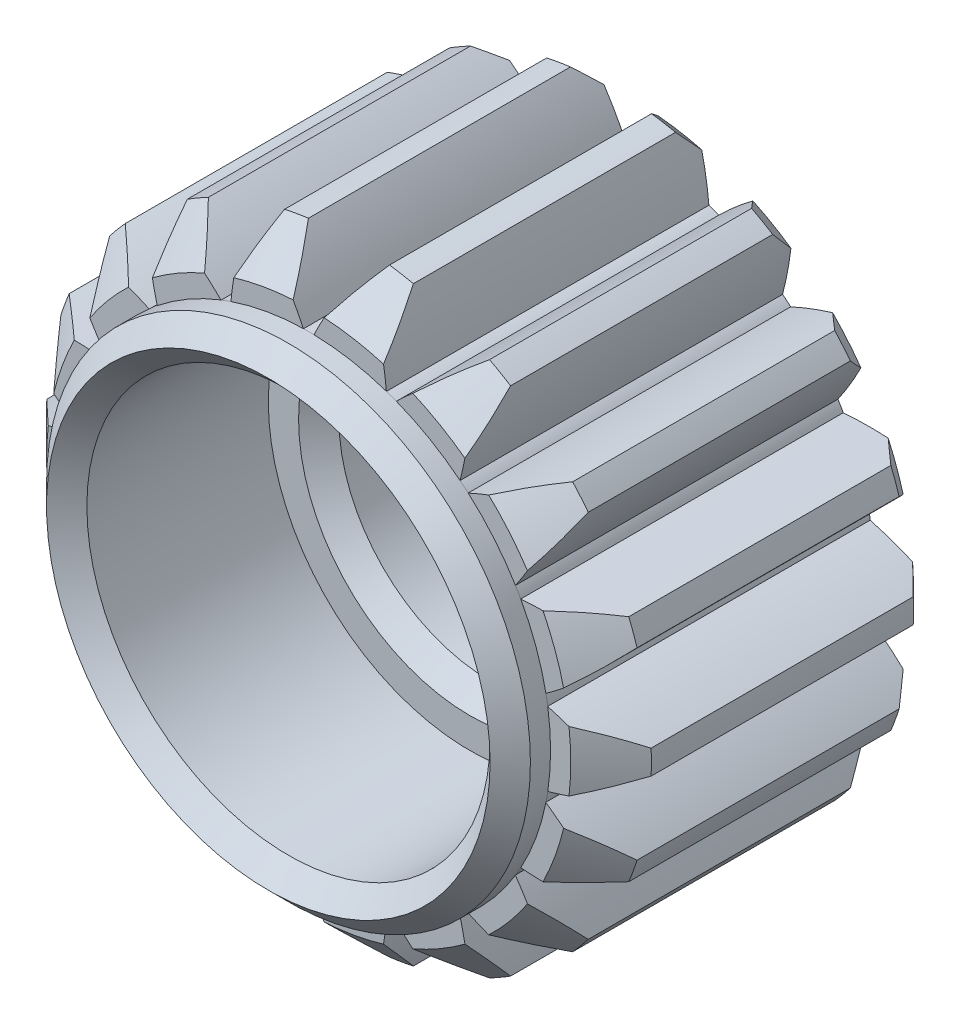
SolidWorks part; units mm, degrees
ref_plane "Front Plane" through (0, 0, 0) normal (0, 0, 1) x (1, 0, 0)
ref_plane "Top Plane" through (0, 0, 0) normal (0, 1, 0) x (1, 0, 0)
ref_plane "Right Plane" through (0, 0, 0) normal (1, 0, 0) x (0, 0, -1)
sketch "Sketch1" plane through (0, 0, 0) normal (0, 0, 1) x (1, 0, 0)
  circle A0 centre (0, 0) radius 7.5
  dimension "D1" = 15
extrude "Boss-Extrude1" add sketch "Sketch1" along normal mid plane 8
chamfer "Front Chamfer" distance 1 angle 45 1 edges at (7.5, 0, 4)
chamfer "Rear Chamfer" distance 0.5 angle 45 1 edges at (7.5, 0, -4)
sketch "Sketch2" plane through (0, 0, 4) normal (0, 0, 1) x (1, 0, 0)
  line L3 (-11.4306, 0) -> (12.9819, 0) construction
  line L4 (0, 0) -> (0, 7.5) construction
  line L5 (0, 0) -> (1.0049, 7.4324) construction
  line L6 (0, 0) -> (-1.0049, 7.4324) construction
  line L7 (0, 0) -> (0.1418, 6.4985) construction
  line L8 (0, 0) -> (-0.1418, 6.4985) construction
  arc A0 (-1.0049, 7.4324) -> (1.0049, 7.4324) centre (0, 0) cw
  circle A4 centre (0, 0) radius 7.5 construction
  circle A5 centre (0, 0) radius 6.5 construction
  arc A6 (-1.0049, 7.4324) -> (-0.1308, 5.9943) centre (-7.3662, 2.5812) cw
  arc A7 (1.0049, 7.4324) -> (0.1308, 5.9943) centre (7.3662, 2.5812) ccw
  arc A8 (-0.1308, 5.9943) -> (0.1308, 5.9943) centre (0, 4.5) cw
  point P20 (0, 0)
  point P21 (0, 0)
  point P22 (0, 6)
  point P23 (-0.5303, 5.9031)
  point P24 (-0.5538, 5.894)
  point P25 (0, 0)
  point P26 (0.5488, 5.896)
  point P27 (0, 0)
  point P28 (0.4501, 5.9422)
  point P29 (0.2798, 5.9777)
  dimension "D1" = 7.7
  dimension "D2" = 15.4
  dimension "D4" = 8
  dimension "D5" = 3
  dimension "D6" = 1.5
  dimension "D7" = 7.8053
  dimension "D9" = 2.5
  dimension "D3" = 7.7
  dimension "D8" = 2.0098
extrude "Cut-Extrude1" cut sketch "Sketch2" against normal through all
pattern_circular "CirPattern1" count 18 over 360 about axis through (0, 0, 3) along (0, 0, -1) of "Cut-Extrude1"
sketch "Sketch3" plane through (0, 0, 4) normal (0, 0, 1) x (1, 0, 0)
  circle A72 centre (0, 0) radius 6
  arc A75 (1.9273, -5.6775) -> (2.1731, -5.5881) centre (1.5391, -4.2286) ccw construction
extrude "Boss-Extrude2" add sketch "Sketch3" along normal blind 1
chamfer "Chamfer3" distance 0.5 angle 45 1 edges at (6, 0, 5)
sketch "Sketch4" plane through (0, 0, 5) normal (0, 0, 1) x (1, 0, 0)
  circle A0 centre (0, 0) radius 5
  dimension "D1" = 10
extrude "Cut-Extrude2" cut sketch "Sketch4" against normal blind 5
sketch "Sketch5" plane through (0, 0, 0) normal (0, 0, 1) x (1, 0, 0)
  circle A0 centre (0, 0) radius 3.75
  dimension "D1" = 7.5
extrude "Cut-Extrude3" cut sketch "Sketch5" against normal through all
chamfer "Chamfer4" distance 0.5 angle 45 2 edges at (5, 0, 5) (3.75, 0, 0)
chamfer "Chamfer5" distance 2 angle 45 1 edges at (3.75, 0, -4)
